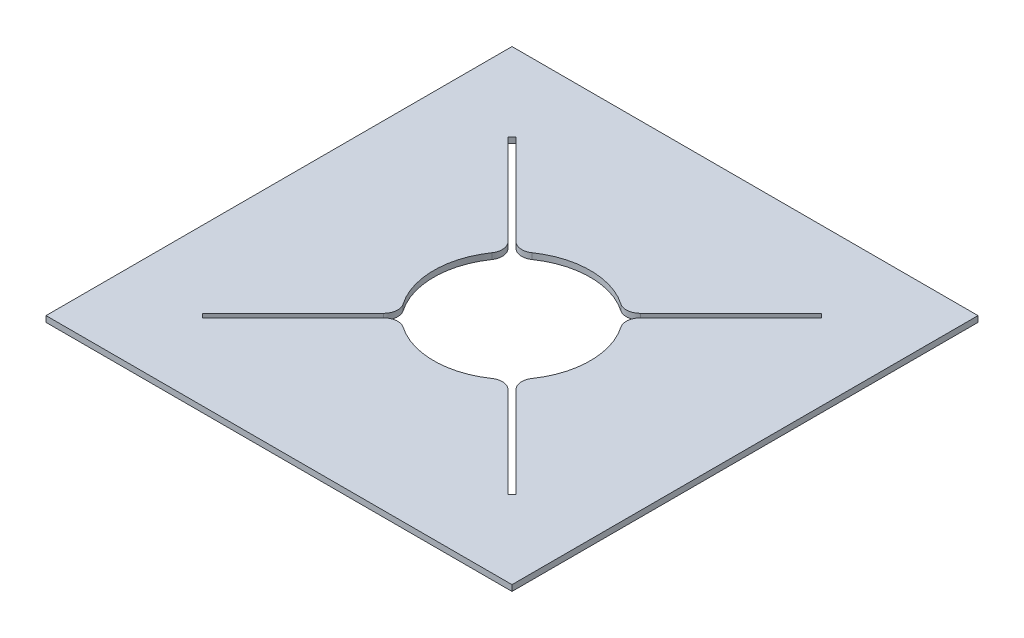
SolidWorks part; units mm, degrees
ref_plane "Front Plane" through (0, 0, 0) normal (0, 0, 1) x (1, 0, 0)
ref_plane "Top Plane" through (0, 0, 0) normal (0, 1, 0) x (1, 0, 0)
ref_plane "Right Plane" through (0, 0, 0) normal (1, 0, 0) x (0, 0, -1)
sketch "Sketch1" plane through (0, 0, 0) normal (0, 1, 0) x (1, 0, 0)
  line L1 (-201.9624, 164.5437) -> (298.0376, 164.5437)
  line L2 (-201.9624, 164.5437) -> (-201.9624, -335.4563)
  line L3 (-201.9624, -335.4563) -> (298.0376, -335.4563)
  line L4 (298.0376, 164.5437) -> (298.0376, -335.4563)
  dimension "D1" = 500
  dimension "D2" = 500
extrude "Boss-Extrude1" add sketch "Sketch1" along normal blind 6.35
sketch "Sketch2" plane through (0, 6.35, 0) normal (0, 1, 0) x (1, 0, 0)
  circle A0 centre (48.0376, -85.4563) radius 84
  dimension "D1" = 168
extrude "Cut-Extrude1" cut sketch "Sketch2" against normal blind 6.35
sketch "Sketch3" plane through (0, 6.35, 0) normal (0, 1, 0) x (1, 0, 0)
  line L0 (48.0376, -85.4563) -> (-118.1325, 80.7138)
  line L1 (216.329, 78.5925) -> (103.1919, -34.5446)
  line L2 (-120.2538, 78.5925) -> (-116.0112, 82.8351)
  line L3 (-120.2538, 78.5925) -> (-7.1167, -34.5446)
  line L4 (-7.1167, -34.5446) -> (-2.8741, -30.3019)
  line L5 (-116.0112, 82.8351) -> (-2.8741, -30.3019)
  line L6 (212.0864, 82.8351) -> (98.9493, -30.3019)
  line L7 (98.9493, -30.3019) -> (103.1919, -34.5446)
  line L8 (212.0864, 82.8351) -> (216.329, 78.5925)
  line L9 (212.0864, -253.7477) -> (98.9493, -140.6106)
  line L10 (216.329, -249.505) -> (103.1919, -136.368)
  line L11 (103.1919, -136.368) -> (98.9493, -140.6106)
  line L12 (216.329, -249.505) -> (212.0864, -253.7477)
  line L13 (-120.2538, -249.505) -> (-7.1167, -136.368)
  line L14 (-116.0112, -253.7477) -> (-2.8741, -140.6106)
  line L15 (-2.8741, -140.6106) -> (-7.1167, -136.368)
  line L16 (-116.0112, -253.7477) -> (-120.2538, -249.505)
  point P2 (-4.9954, -32.4233)
  point P23 (48.0376, -85.4563)
  dimension "D1" = 235
  dimension "D2" = 0
  dimension "D3" = 0
  dimension "D4" = 160
  dimension "D5" = 6
  dimension "D6" = 4
extrude "Cut-Extrude3" cut sketch "Sketch3" against normal blind 6.35 contours L6 L7 L1 L8 | L5 L4 L3 L2 | L15 L13 L16 L14 | L9 L11 L10 L12
fillet "Fillet1" radius 15 8 edges at (105.2754, 3.175, 23.9759) (109.518, 3.175, 28.2185) (109.518, 3.175, 142.694) (105.2754, 3.175, 146.9367) (-9.2002, 3.175, 146.9367) (-13.4428, 3.175, 142.694) (-13.4428, 3.175, 28.2185) (-9.2002, 3.175, 23.9759)
